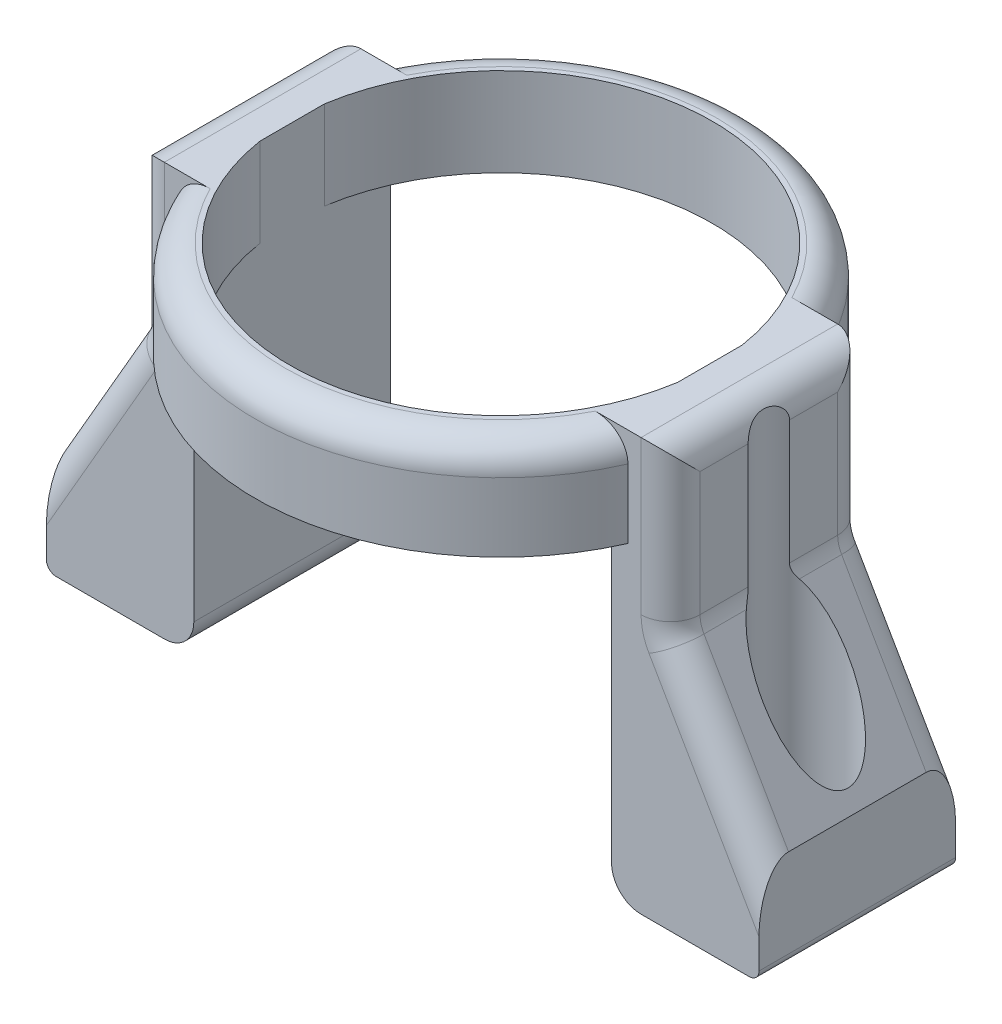
SolidWorks part; units mm, degrees
ref_plane "Спереди" through (0, 0, 0) normal (0, 0, 1) x (1, 0, 0)
ref_plane "Сверху" through (0, 0, 0) normal (0, 1, 0) x (1, 0, 0)
ref_plane "Справа" through (0, 0, 0) normal (1, 0, 0) x (0, 0, -1)
sketch "Эскиз1" plane through (0, 0, 0) normal (0, 1, 0) x (1, 0, 0)
  circle A0 centre (0, 0) radius 25
  circle A1 centre (0, 0) radius 21.5
  dimension "D1" = 50
  dimension "D2" = 43
extrude "Бобышка-Вытянуть1" add sketch "Эскиз1" along normal blind 10
sketch "Эскиз2" plane through (0, 10, 0) normal (0, -1, 0) x (-1, 0, 0)
  line L0 (31.3877, 0) -> (-43.976, 0) construction
  line L1 (0, -12.8215) -> (0, 11.0564) construction
  line L2 (-21.25, 10) -> (-27.25, 10)
  line L3 (-21.25, 10) -> (-21.25, -10)
  line L4 (-21.25, -10) -> (-27.25, -10)
  line L5 (-27.25, 10) -> (-27.25, -10)
  line L6 (-24.25, -10) -> (-24.25, 10) construction
  line L7 (-21.25, 0) -> (-27.25, 0) construction
  line L8 (21.25, -10) -> (27.25, -10)
  line L9 (27.25, 10) -> (27.25, -10)
  line L10 (21.25, 10) -> (27.25, 10)
  line L11 (21.25, 10) -> (21.25, -10)
  point P3 (-24.25, 0)
  dimension "D1" = 6
  dimension "D2" = 42.5
  dimension "D3" = 20
extrude "Бобышка-Вытянуть2" add sketch "Эскиз2" along normal blind 42
sketch "Эскиз3" plane through (0, -32, 0) normal (0, -1, 0) x (1, 0, 0)
  line L0 (0, 14.4616) -> (0, -9.395) construction
  line L1 (21.25, 10) -> (36.25, 10)
  line L2 (21.25, 10) -> (21.25, -10)
  line L3 (21.25, -10) -> (36.25, -10)
  line L4 (36.25, 10) -> (36.25, -10)
  line L5 (-21.25, -10) -> (-36.25, -10)
  line L6 (-36.25, 10) -> (-36.25, -10)
  line L7 (-21.25, 10) -> (-36.25, 10)
  line L8 (-21.25, 10) -> (-21.25, -10)
  dimension "D1" = 15
extrude "Бобышка-Вытянуть3" add sketch "Эскиз3" against normal blind 10
sketch "Эскиз4" plane through (0, -32, 0) normal (0, -1, 0) x (1, 0, 0)
  line L0 (-45.1049, 0) -> (52.4352, 0) construction
  line L1 (0, 13.0448) -> (0, -11.8624) construction
  circle A0 centre (31, 0) radius 2.3
  circle A1 centre (-31, 0) radius 2.3
  dimension "D1" = 62
  dimension "D2" = 4.6
extrude "Вырез-Вытянуть1" cut sketch "Эскиз4" against normal through all
chamfer "Фаска2" distance 9 angle 60 2 edges at (27.25, -22, 0) (-27.25, -22, 0) first distance on face at (31, -22, -2.3) first distance on face at (-31, -22, 2.3)
fillet "Скругление1" radius 3 16 edges at (31.75, -14.2058, -10) (31.75, -14.2058, 10) (-31.75, -14.2058, 10) (-31.75, -14.2058, -10) (27.25, 10, 0) (27.25, 1.7942, -10) (27.25, -6.4115, 0) (27.25, 1.7942, 10) (-27.25, 10, 0) (-27.25, 1.7942, 10) (-27.25, -6.4115, 0) (-27.25, 1.7942, -10) (0, 10, 25) (0, 10, -25) (-21.25, -32, 0) (21.25, -32, 0)
sketch "Эскиз5" plane through (0, 10, 0) normal (0, 1, 0) x (1, 0, 0)
  line L0 (-44.1555, 0) -> (41.7494, 0) construction
  line L1 (41.7494, 0) -> (0, 0) construction
  line L2 (0, 0) -> (0, 14.2862) construction
  circle A0 centre (31, 0) radius 4.3
  circle A1 centre (-31, 0) radius 4.3
  dimension "D1" = 8.6
  dimension "D2" = 62
extrude "Вырез-Вытянуть2" cut sketch "Эскиз5" against normal blind 37
chamfer "Фаска3" distance 1 angle 60 2 edges at (0, 0, -21.5) (0, 0, 21.5) first distance on face at (0, 5, -12.3846) first distance on face at (0, 5, 12.3846)
chamfer "Фаска4" distance 2 angle 45 1 edges at (31, -27, 2.3)
fillet "Скругление2" radius 1 2 edges at (36.25, -32, 0) (-36.25, -32, 0)
